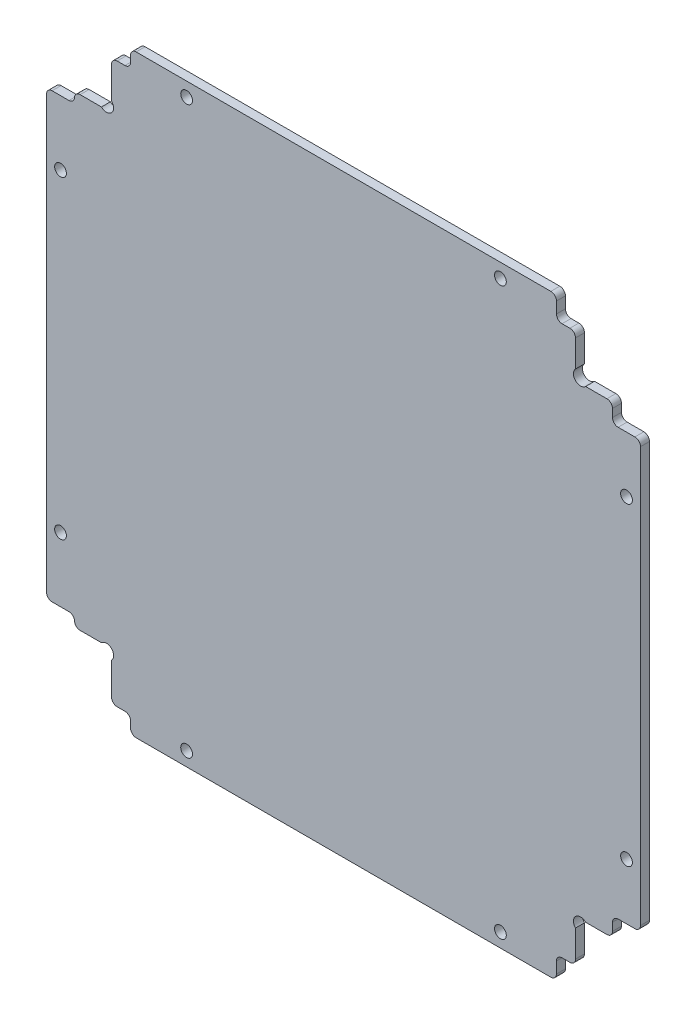
SolidWorks part; units mm, degrees
material "FR4_stuffedProtoboard"
ref_plane "Front Plane" through (0, 0, 0) normal (0, 0, 1) x (1, 0, 0)
ref_plane "Top Plane" through (0, 0, 0) normal (0, 1, 0) x (1, 0, 0)
ref_plane "Right Plane" through (0, 0, 0) normal (1, 0, 0) x (0, 0, -1)
sketch "Sketch1" plane through (0, 0, 0) normal (0, 0, 1) x (1, 0, 0)
  line L0 (53, 53) -> (-53, -53) construction
  line L1 (53, 53) -> (-53, 53)
  line L2 (53, 53) -> (53, -53)
  line L3 (53, -53) -> (-53, -53)
  line L4 (-53, 53) -> (-53, -53)
  point P4 (0, 0)
  dimension "D1" = 106
  dimension "D2" = 106
extrude "mainOutline" add sketch "Sketch1" along normal blind 1.6
sketch "axisLabels" plane through (0, 0, 0) normal (0, 0, -1) x (-1, 0, 0)
  text T0 "+Y"
  text T1 "+X"
sketch "Sketch4" plane through (0, 0, 0) normal (0, 0, -1) x (-1, 0, 0)
  line L1 (-41.4, -41.4) -> (-48, -41.4)
  line L3 (-41.4, -49) -> (-41.4, -41.4)
  line L5 (-60.1065, -39) -> (-49.9975, -39)
  line L7 (-39, -61.4521) -> (-39, -49.9)
  line L9 (39, -56.2753) -> (39, -49.9)
  line L10 (-53, 53) -> (53, 53) construction
  line L11 (41.4, -49.9) -> (41.4, -41.4)
  line L12 (-53, -53) -> (-53, 53) construction
  line L13 (41.4, -41.4) -> (48, -41.4)
  line L15 (48, -40.5) -> (55.5177, -40.5)
  line L17 (55.3838, 40.5) -> (48, 40.5)
  line L19 (39, 57.6877) -> (39, 49.9)
  line L21 (-39, 59.8804) -> (-39, 49.9)
  line L23 (-56.8428, 39) -> (-49.9975, 39)
  line L25 (-41.4, 41.4) -> (-41.4, 49)
  line L27 (-48, 41.4) -> (-41.4, 41.4)
  line L29 (41.4, 49.9) -> (41.4, 41.4)
  line L31 (48, 41.4) -> (41.4, 41.4)
  line L32 (-48, 41.4) -> (-48, 39)
  line L33 (-48, 39) -> (-49.9975, 39)
  line L34 (-41.4, 49) -> (-39, 49)
  line L35 (-39, 49) -> (-39, 49.9)
  line L36 (48, 40.5) -> (48, 41.4)
  line L37 (39, 49.9) -> (41.4, 49.9)
  line L38 (48, -40.5) -> (48, -41.4)
  line L39 (39, -49.9) -> (41.4, -49.9)
  line L40 (-41.4, -49) -> (-39, -49)
  line L41 (-39, -49) -> (-39, -49.9)
  line L42 (-49.9975, -39) -> (-48, -39)
  line L43 (-48, -39) -> (-48, -41.4)
  line L44 (-39, 59.8804) -> (-56.8428, 59.8804)
  line L45 (-56.8428, 59.8804) -> (-56.8428, 39)
  line L46 (53, 53) -> (53, -53) construction
  line L47 (-60.1065, -39) -> (-60.1065, -61.4521)
  line L48 (-60.1065, -61.4521) -> (-39, -61.4521)
  line L49 (39, -56.2753) -> (55.5177, -56.2753)
  line L50 (55.5177, -56.2753) -> (55.5177, -40.5)
  line L51 (55.3838, 40.5) -> (55.3838, 57.6877)
  line L52 (55.3838, 57.6877) -> (39, 57.6877)
  line L53 (53, -53) -> (-53, -53) construction
  dimension "D1" = 14
  dimension "D2" = 11.6
  dimension "D3" = 5
  dimension "D4" = 12.5
  dimension "D5" = 11.6
  dimension "D6" = 3.1
  dimension "D7" = 12.5
  dimension "D8" = 14
  dimension "D9" = 3.1
  dimension "D10" = 5
  dimension "D11" = 11.6
  dimension "D12" = 11.6
  dimension "D13" = 14
  dimension "D14" = 14
  dimension "D15" = 11.6
  dimension "D16" = 11.6
  dimension "D17" = 5
  dimension "D18" = 4
  dimension "D19" = 14
  dimension "D20" = 14
  dimension "D21" = 11.6
  dimension "D22" = 11.6
  dimension "D23" = 4
  dimension "D24" = 5
extrude "railCutouts" cut sketch "Sketch4" against normal through all
sketch "Sketch5" plane through (0, 0, 0) normal (0, 0, -1) x (-1, 0, 0)
  line L0 (-48.898, -39.898) -> (-52.4015, -43.4015) construction
  line L1 (-48, -40.7961) -> (-51.5035, -44.2995) construction
  line L2 (-49.7961, -39) -> (-53.2995, -42.5035) construction
  line L3 (-48, -41.4) -> (-48, -39) construction
  line L4 (-48, 39) -> (-48, 41.4) construction
  line L5 (-42.298, -42.298) -> (-45.4445, -45.4445) construction
  line L6 (-41.4, -43.1961) -> (-44.5465, -46.3425)
  line L7 (-43.1961, -41.4) -> (-46.3425, -44.5465)
  line L8 (-39.898, -49.898) -> (-42.6199, -52.6199) construction
  line L9 (-39, -50.7961) -> (-41.7219, -53.5179) construction
  line L10 (-40.7961, -49) -> (-43.5179, -51.7219) construction
  line L11 (39.898, -50.798) -> (41.4231, -52.3231) construction
  line L12 (40.7961, -49.9) -> (42.3212, -51.4251) construction
  line L13 (39, -51.6961) -> (40.5251, -53.2212) construction
  line L14 (42.298, -42.298) -> (44.0402, -44.0402) construction
  line L15 (43.1961, -41.4) -> (44.9382, -43.1422)
  line L16 (41.4, -43.1961) -> (43.1422, -44.9382)
  line L17 (48.898, -41.398) -> (49.9793, -42.4793) construction
  line L18 (49.7961, -40.5) -> (50.8774, -41.5813) construction
  line L19 (48, -42.2961) -> (49.0813, -43.3774) construction
  line L20 (48.898, 41.398) -> (50.5001, 43.0001) construction
  line L21 (48, 42.2961) -> (49.602, 43.8981) construction
  line L22 (49.7961, 40.5) -> (51.3981, 42.102) construction
  line L23 (42.298, 42.298) -> (44.029, 44.029) construction
  line L24 (41.4, 43.1961) -> (43.131, 44.927)
  line L25 (43.1961, 41.4) -> (44.927, 43.131)
  line L26 (39.898, 50.798) -> (41.2638, 52.1638) construction
  line L27 (39, 51.6961) -> (40.3658, 53.0618) construction
  line L28 (40.7961, 49.9) -> (42.1618, 51.2658) construction
  line L29 (-48.898, 39.898) -> (-50.0606, 41.0606) construction
  line L30 (-49.7961, 39) -> (-50.9587, 40.1626) construction
  line L31 (-48, 40.7961) -> (-49.1626, 41.9587) construction
  line L32 (-42.298, 42.298) -> (-43.7968, 43.7968) construction
  line L33 (-43.1961, 41.4) -> (-44.6948, 42.8988)
  line L34 (-41.4, 43.1961) -> (-42.8988, 44.6948)
  line L35 (-39.898, 49.898) -> (-41.256, 51.256) construction
  line L36 (-40.7961, 49) -> (-42.154, 50.358) construction
  line L37 (-39, 50.7961) -> (-40.358, 52.154) construction
  line L38 (-41.4, 41.4) -> (-41.4, 49) construction
  line L39 (-39, 49) -> (-39, 53) construction
  line L40 (39, 53) -> (39, 49.9) construction
  line L41 (41.4, 49.9) -> (41.4, 41.4) construction
  line L42 (48, 41.4) -> (48, 40.5) construction
  line L43 (39, -49.9) -> (39, -53) construction
  line L44 (41.4, -41.4) -> (41.4, -49.9) construction
  line L45 (53, -40.5) -> (48, -40.5) construction
  line L46 (-39, -53) -> (-39, -49) construction
  line L47 (-41.4, -49) -> (-41.4, -41.4) construction
  arc A0 (-48, -40.7961) -> (-49.7961, -39) centre (-48.898, -39.898) ccw construction
  arc A1 (-53.2995, -42.5035) -> (-51.5035, -44.2995) centre (-52.4015, -43.4015) ccw construction
  arc A2 (-41.4, -43.1961) -> (-43.1961, -41.4) centre (-42.298, -42.298) ccw
  arc A3 (-46.3425, -44.5465) -> (-44.5465, -46.3425) centre (-45.4445, -45.4445) ccw
  arc A4 (-39, -50.7961) -> (-40.7961, -49) centre (-39.898, -49.898) ccw construction
  arc A5 (-43.5179, -51.7219) -> (-41.7219, -53.5179) centre (-42.6199, -52.6199) ccw construction
  arc A6 (40.7961, -49.9) -> (39, -51.6961) centre (39.898, -50.798) ccw construction
  arc A7 (40.5251, -53.2212) -> (42.3212, -51.4251) centre (41.4231, -52.3231) ccw construction
  arc A8 (43.1961, -41.4) -> (41.4, -43.1961) centre (42.298, -42.298) ccw
  arc A9 (43.1422, -44.9382) -> (44.9382, -43.1422) centre (44.0402, -44.0402) ccw
  arc A10 (49.7961, -40.5) -> (48, -42.2961) centre (48.898, -41.398) ccw construction
  arc A11 (49.0813, -43.3774) -> (50.8774, -41.5813) centre (49.9793, -42.4793) ccw construction
  arc A12 (48, 42.2961) -> (49.7961, 40.5) centre (48.898, 41.398) ccw construction
  arc A13 (51.3981, 42.102) -> (49.602, 43.8981) centre (50.5001, 43.0001) ccw construction
  arc A14 (41.4, 43.1961) -> (43.1961, 41.4) centre (42.298, 42.298) ccw
  arc A15 (44.927, 43.131) -> (43.131, 44.927) centre (44.029, 44.029) ccw
  arc A16 (39, 51.6961) -> (40.7961, 49.9) centre (39.898, 50.798) ccw construction
  arc A17 (42.1618, 51.2658) -> (40.3658, 53.0618) centre (41.2638, 52.1638) ccw construction
  arc A18 (-49.7961, 39) -> (-48, 40.7961) centre (-48.898, 39.898) ccw construction
  arc A19 (-49.1626, 41.9587) -> (-50.9587, 40.1626) centre (-50.0606, 41.0606) ccw construction
  arc A20 (-43.1961, 41.4) -> (-41.4, 43.1961) centre (-42.298, 42.298) ccw
  arc A21 (-42.8988, 44.6948) -> (-44.6948, 42.8988) centre (-43.7968, 43.7968) ccw
  arc A22 (-40.7961, 49) -> (-39, 50.7961) centre (-39.898, 49.898) ccw construction
  arc A23 (-40.358, 52.154) -> (-42.154, 50.358) centre (-41.256, 51.256) ccw construction
  point P2 (-50.6498, -41.6498)
  point P9 (-43.8713, -43.8713)
  point P17 (-41.259, -51.259)
  point P24 (40.6606, -51.5606)
  point P31 (43.1691, -43.1691)
  point P38 (49.4387, -41.9387)
  point P45 (49.699, 42.199)
  point P52 (43.1635, 43.1635)
  point P59 (40.5809, 51.4809)
  point P66 (-49.4793, 40.4793)
  point P73 (-43.0474, 43.0474)
  point P80 (-40.577, 50.577)
  dimension "D14" = 1.27
  dimension "D1" = 45
  dimension "D3" = 45
  dimension "D4" = 45
  dimension "D5" = 45
  dimension "D6" = 45
  dimension "D7" = 45
  dimension "D8" = 45
  dimension "D9" = 45
  dimension "D10" = 45
  dimension "D11" = 45
  dimension "D12" = 45
  dimension "D13" = 45
extrude "dogbones" cut sketch "Sketch5" against normal through all
sketch "Sketch6" plane through (0, 0, 0) normal (0, 0, -1) x (-1, 0, 0)
  line L0 (-39, 50) -> (-39, 53) construction
  line L1 (-39, 49) -> (-39, 53) construction
  line L2 (-39, 53) -> (39, 53) construction
  line L3 (-40, 50) -> (-40, 53)
  line L4 (-38, 50) -> (-38, 53)
  line L5 (-49, 39) -> (-53, 39) construction
  line L6 (-53, 39) -> (-48, 39) construction
  line L7 (-49, 38) -> (-53, 38)
  line L8 (-49, 40) -> (-53, 40)
  line L9 (-49, -39) -> (-55.2142, -39) construction
  line L10 (-48, -39) -> (-53, -39) construction
  line L11 (-49, -40) -> (-55.2142, -40)
  line L12 (-49, -38) -> (-55.2142, -38)
  line L13 (-39, -50) -> (-39, -53.9161) construction
  line L14 (-39, -53) -> (-39, -49) construction
  line L15 (-38, -50) -> (-38, -53.9161)
  line L16 (-40, -50) -> (-40, -53.9161)
  line L17 (39, -50.9) -> (39, -54.538) construction
  line L18 (39, -49.9) -> (39, -53) construction
  line L19 (40, -50.9) -> (40, -54.538)
  line L20 (38, -50.9) -> (38, -54.538)
  line L21 (49, -40.5) -> (54.2026, -40.5) construction
  line L22 (53, -40.5) -> (48, -40.5) construction
  line L23 (49, -39.5) -> (54.2026, -39.5)
  line L24 (49, -41.5) -> (54.2026, -41.5)
  line L25 (49, 40.5) -> (54.5566, 40.5) construction
  line L26 (48, 40.5) -> (53, 40.5) construction
  line L27 (49, 41.5) -> (54.5566, 41.5)
  line L28 (49, 39.5) -> (54.5566, 39.5)
  line L29 (39, 50.9) -> (39, 55.8281) construction
  line L30 (39, 53) -> (39, 49.9) construction
  line L31 (38, 50.9) -> (38, 55.8281)
  line L32 (40, 50.9) -> (40, 55.8281)
  line L33 (-48, -41.4) -> (-48, -39) construction
  line L34 (-39, -49) -> (-41.4, -49) construction
  line L35 (41.4, -49.9) -> (39, -49.9) construction
  line L36 (48, -40.5) -> (48, -41.4) construction
  line L37 (48, 41.4) -> (48, 40.5) construction
  line L38 (39, 49.9) -> (41.4, 49.9) construction
  arc A0 (-40, 50) -> (-38, 50) centre (-39, 50) ccw
  arc A1 (-38, 53) -> (-40, 53) centre (-39, 53) ccw
  arc A2 (-49, 38) -> (-49, 40) centre (-49, 39) ccw
  arc A3 (-53, 40) -> (-53, 38) centre (-53, 39) ccw
  arc A4 (-49, -40) -> (-49, -38) centre (-49, -39) ccw
  arc A5 (-55.2142, -38) -> (-55.2142, -40) centre (-55.2142, -39) ccw
  arc A6 (-38, -50) -> (-40, -50) centre (-39, -50) ccw
  arc A7 (-40, -53.9161) -> (-38, -53.9161) centre (-39, -53.9161) ccw
  arc A8 (40, -50.9) -> (38, -50.9) centre (39, -50.9) ccw
  arc A9 (38, -54.538) -> (40, -54.538) centre (39, -54.538) ccw
  arc A10 (49, -39.5) -> (49, -41.5) centre (49, -40.5) ccw
  arc A11 (54.2026, -41.5) -> (54.2026, -39.5) centre (54.2026, -40.5) ccw
  arc A12 (49, 41.5) -> (49, 39.5) centre (49, 40.5) ccw
  arc A13 (54.5566, 39.5) -> (54.5566, 41.5) centre (54.5566, 40.5) ccw
  arc A14 (38, 50.9) -> (40, 50.9) centre (39, 50.9) ccw
  arc A15 (40, 55.8281) -> (38, 55.8281) centre (39, 55.8281) ccw
  point P6 (-39, 51.5)
  point P11 (-51, 39)
  point P21 (-52.1071, -39)
  point P30 (-39, -51.958)
  point P39 (39, -52.719)
  point P48 (51.6013, -40.5)
  point P57 (51.7783, 40.5)
  point P66 (39, 53.364)
  point P75 (-39, 49)
  dimension "D1" = 1
extrude "solarFillets" cut sketch "Sketch6" against normal through all
fillet "handlingFillets" radius 1 16 edges at (-41.4, -49.9, 0.8) (-38, -53, 0.8) (-53, -39.5, 0.8) (-48, -41.4, 0.8) (-48, 41.4, 0.8) (-53, 39.5, 0.8) (-41.4, 49.9, 0.8) (-38, 53, 0.8) (38, 53, 0.8) (41.4, 49, 0.8) (48, 41.4, 0.8) (53, 38, 0.8) (53, -38, 0.8) (48, -41.4, 0.8) (41.4, -49, 0.8) (38, -53, 0.8)
sketch "Sketch7" plane through (0, 0, 1.6) normal (0, 0, 1) x (1, 0, 0)
  line L0 (-37, -53) -> (37, -53) construction
  line L1 (-53, 38.5) -> (-53, -38.5) construction
  line L2 (37, 53) -> (-37, 53) construction
  line L3 (-31.37, 28.67) -> (-31.37, 31.21) construction
  line L4 (-31.37, 31.21) -> (-28.83, 31.21) construction
  line L5 (-28.83, 31.21) -> (-28.83, 28.67) construction
  line L6 (-28.83, 28.67) -> (-31.37, 28.67) construction
  line L7 (-31.37, 28.67) -> (-28.83, 31.21) construction
  circle A1 centre (-28.4723, -17.925) radius 0.8
  circle A3 centre (-28.4723, -33.775) radius 0.8
  circle A5 centre (-31.37, 28.67) radius 0.425
  circle A7 centre (-28.83, 28.67) radius 0.425
  circle A9 centre (-30.1, 29.94) radius 0.425
  circle A10 centre (-28.83, 31.21) radius 0.425
  circle A11 centre (-31.37, 31.21) radius 0.425
  circle A12 centre (-31.37, 21.27) radius 0.425
  circle A13 centre (-28.83, 21.27) radius 0.425
  circle A14 centre (-30.1, 22.54) radius 0.425
  circle A15 centre (-28.83, 23.81) radius 0.425
  circle A16 centre (-31.37, 23.81) radius 0.425
  circle A17 centre (-31.37, 13.87) radius 0.425
  circle A18 centre (-28.83, 13.87) radius 0.425
  circle A19 centre (-30.1, 15.14) radius 0.425
  circle A20 centre (-28.83, 16.41) radius 0.425
  circle A21 centre (-31.37, 16.41) radius 0.425
  point P13 (-30.1, 29.94)
  dimension "D8" = 1.6
  dimension "D9" = 3
  dimension "D6" = 0.85
  dimension "D1" = 19.225
  dimension "D2" = 24.5277
  dimension "D3" = 15.85
  dimension "D4" = 23.06
  dimension "D5" = 22.9
  dimension "D7" = 2.54
  dimension "D10" = 7.4
extrude "connectorHoles" [suppressed] cut sketch "Sketch7" against normal through all
hole_wizard "M2 Clearance Hole1" positions "Sketch8" profile "Sketch9" hole size "M2" standard "ANSI Metric" end condition through all
sketch "Sketch8" plane through (0, 0, 0) normal (0, 0, -1) x (-1, 0, 0)
  line L0 (53, 38.5) -> (53, -38.5) construction
  line L1 (37, -53) -> (-37, -53) construction
  line L2 (-53, -37) -> (-53, 37) construction
  line L3 (53, 0) -> (-53, 0) construction
  line L5 (0, -53) -> (0, -11.6379) construction
  point P0 (50.5, -28)
  point P1 (28, -50.5)
  point P5 (-50.5, -28)
  point P30 (-28, -50.5)
  point P31 (-28, 50.5)
  point P32 (-50.5, 28)
  point P33 (28, 50.5)
  point P34 (50.5, 28)
  dimension "D1" = 2.5
  dimension "D2" = 2.5
  dimension "D4" = 2.5
  dimension "D5" = 25
  dimension "D6" = 25
  dimension "D7" = 25
sketch "Sketch9" plane through (-50.5, -28, 0) normal (1, 0, 0) x (0, 1, 0)
  line L0 (0, 0) -> (0, 1.6)
  line L1 (0, 1.6) -> (1.05, 1.6)
  line L2 (1.05, 1.6) -> (1.05, 0)
  line L5 (1.05, 0) -> (0, 0)
  line L11 (0, -6.35) -> (0, 107.95) construction
  dimension "Thru Hole Dia." = 2.1
  dimension "Thru Hole Depth" = 1.6
